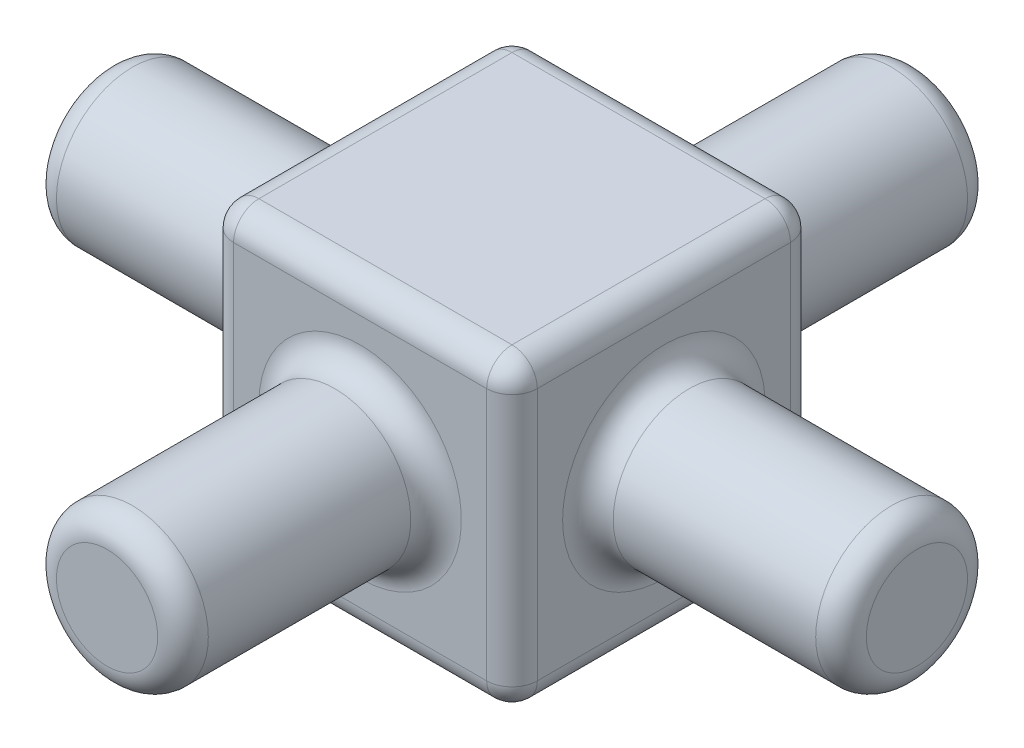
SolidWorks part; units mm, degrees
ref_plane "前视基准面" through (0, 0, 0) normal (0, 0, 1) x (1, 0, 0)
ref_plane "上视基准面" through (0, 0, 0) normal (0, 1, 0) x (1, 0, 0)
ref_plane "右视基准面" through (0, 0, 0) normal (1, 0, 0) x (0, 0, -1)
sketch "草图1" plane through (0, 0, 0) normal (0, 1, 0) x (1, 0, 0)
  line L1 (-3, -3) -> (3, -3)
  line L2 (-3, -3) -> (-3, 3)
  line L3 (-3, 3) -> (3, 3)
  line L4 (3, -3) -> (3, 3)
  line L5 (-3, -3) -> (3, 3) construction
  line L6 (-3, 3) -> (3, -3) construction
  point P0 (0, 0)
  dimension "D1" = 6
  dimension "D2" = 6
extrude "凸台-拉伸1" add sketch "草图1" along normal mid plane 6
sketch "草图2" plane through (0, 0, 3) normal (0, 0, 1) x (1, 0, 0)
  circle A0 centre (0, 0) radius 1.5
  dimension "D1" = 3
extrude "凸台-拉伸2" add sketch "草图2" along normal blind 5
ref_axis "基准轴1" through (0, 0, 0) along (0, 1, 0)
pattern_circular "阵列(圆周)1" count 4 every 90 about axis through (0, 0, 0) along (0, 1, 0) of "凸台-拉伸2"
fillet "圆角1" radius 0.5 20 edges at (-8, 0, 1.5) (-1.5, 0, -8) (1.5, 0, 8) (8, 0, -1.5) (3, 0, -1.5) (0, -3, 3) (-3, -3, 0) (3, 0, -3) (3, -3, 0) (0, -3, -3) (-1.5, 0, -3) (-3, 0, -3) (0, 3, -3) (-3, 3, 0) (-3, 0, 3) (-3, 0, 1.5) (1.5, 0, 3) (3, 0, 3) (0, 3, 3) (3, 3, 0)
